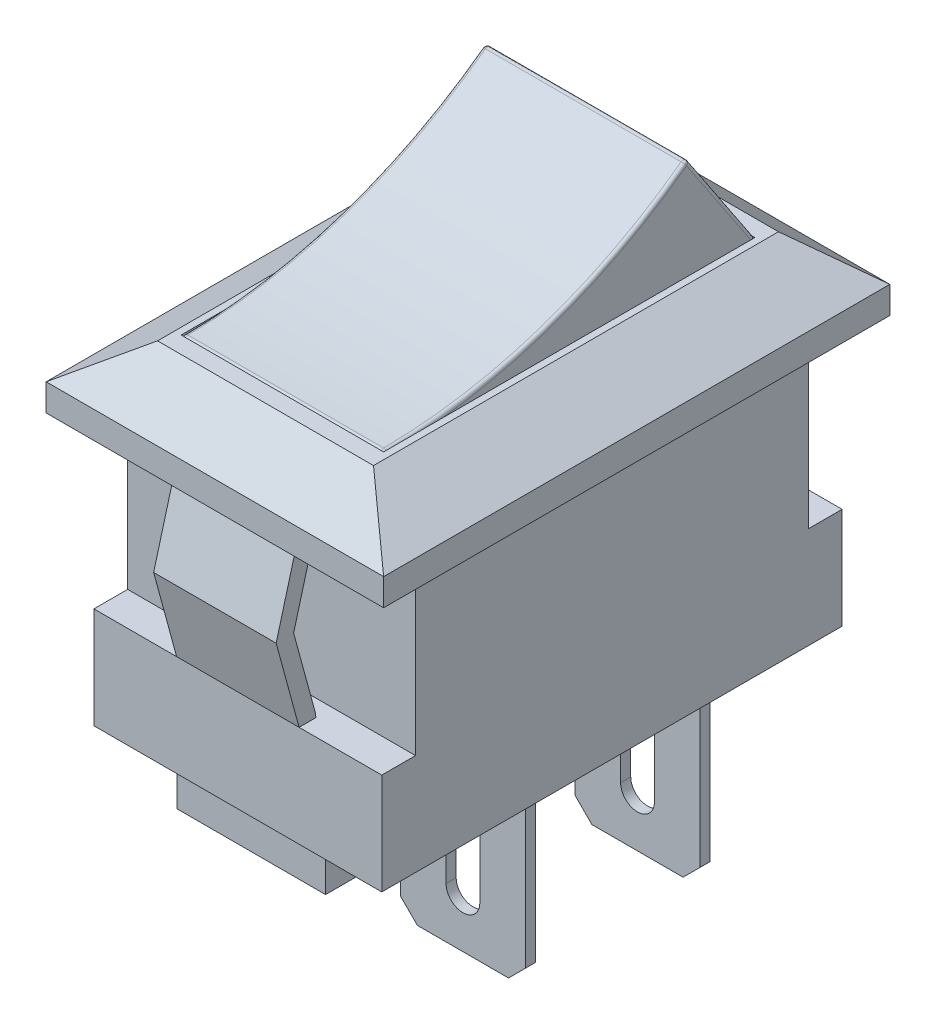
SolidWorks part; units mm, degrees
ref_plane "Front Plane" through (0, 0, 0) normal (0, 0, 1) x (1, 0, 0)
ref_plane "Top Plane" through (0, 0, 0) normal (0, 1, 0) x (1, 0, 0)
ref_plane "Right Plane" through (0, 0, 0) normal (1, 0, 0) x (0, 0, -1)
sketch "Sketch1" plane through (0, 0, 0) normal (0, 1, 0) x (1, 0, 0)
  line L1 (4.265, -6.82) -> (-4.265, -6.82)
  line L2 (4.265, -6.82) -> (4.265, 6.82)
  line L3 (4.265, 6.82) -> (-4.265, 6.82)
  line L4 (-4.265, -6.82) -> (-4.265, 6.82)
  line L5 (4.265, -6.82) -> (-4.265, 6.82) construction
  line L6 (4.265, 6.82) -> (-4.265, -6.82) construction
  point P0 (0, 0)
  dimension "D1" = 13.64
  dimension "D2" = 8.53
extrude "Boss-Extrude1" add sketch "Sketch1" along normal blind 10
sketch "Sketch2" plane through (-4.265, 0, 0) normal (-1, 0, 0) x (0, 0, 1)
  line L0 (-6.82, 10) -> (-6.82, 0) construction
  line L1 (-6.82, 3) -> (-5.82, 3)
  line L2 (-6.82, 3) -> (-6.82, 8)
  line L3 (-6.82, 8) -> (-5.82, 8)
  line L4 (-5.82, 3) -> (-5.82, 8)
  line L5 (6.82, 10) -> (6.82, 0) construction
  line L6 (6.82, 8) -> (5.82, 8)
  line L7 (6.82, 8) -> (6.82, 3)
  line L8 (6.82, 3) -> (5.82, 3)
  line L9 (5.82, 8) -> (5.82, 3)
  line L10 (-6.82, 0) -> (6.82, 0) construction
  line L11 (-6.82, 10) -> (6.82, 10) construction
  dimension "D1" = 1
  dimension "D2" = 1
  dimension "D3" = 3
  dimension "D4" = 3
  dimension "D5" = 2
extrude "Cut-Extrude1" cut sketch "Sketch2" against normal through all
sketch "Sketch3" plane through (0, 10, 0) normal (0, 1, 0) x (1, 0, 0)
  line L1 (3, -5.5) -> (-3, -5.5)
  line L2 (3, -5.5) -> (3, 5.5)
  line L3 (3, 5.5) -> (-3, 5.5)
  line L4 (-3, -5.5) -> (-3, 5.5)
  line L5 (3, -5.5) -> (-3, 5.5) construction
  line L6 (3, 5.5) -> (-3, -5.5) construction
  point P0 (0, 0)
  dimension "D1" = 11
  dimension "D2" = 6
extrude "Cut-Extrude2" cut sketch "Sketch3" against normal blind 0.5
sketch "Sketch4" plane through (0, 10, 0) normal (0, 1, 0) x (1, 0, 0)
  line L1 (5, -7.5) -> (-5, -7.5)
  line L2 (5, -7.5) -> (5, 7.5)
  line L3 (5, 7.5) -> (-5, 7.5)
  line L4 (-5, -7.5) -> (-5, 7.5)
  line L5 (5, -7.5) -> (-5, 7.5) construction
  line L6 (5, 7.5) -> (-5, -7.5) construction
  point P0 (0, 0)
  line M5 (-3, -5.5) -> (-3, 5.5)
  line M6 (-3, 5.5) -> (3, 5.5)
  line M7 (3, 5.5) -> (3, -5.5)
  line M8 (3, -5.5) -> (-3, -5.5)
  line M9 (-4.265, 6.82) -> (-4.265, -6.82)
  line M10 (-4.265, -6.82) -> (4.265, -6.82)
  line M11 (4.265, -6.82) -> (4.265, 6.82)
  line M12 (4.265, 6.82) -> (-4.265, 6.82)
  dimension "D1" = 10
  dimension "D2" = 15
extrude "Boss-Extrude2" add sketch "Sketch4" against normal up to vertex (2 mm away) contours L4 L1 L2 L3 M9 M12 M11 M10 | M12 M9 M10 M11 M8 M5 M6 M7 region at (0, 10, 7.3197) region at (0, 10, -6.6591) up to point (4.265, 8, 6.82)
sketch "Sketch5" plane through (0, 10, 0) normal (0, 1, 0) x (1, 0, 0)
  line L8 (-3.5, 6) -> (-3.5, -6)
  line L9 (-3.5, -6) -> (3.5, -6)
  line L10 (3.5, -6) -> (3.5, 6)
  line L11 (3.5, 6) -> (-3.5, 6)
  line L12 (-3.5, 6) -> (-3.5, -6) construction
  line L13 (-3.5, -6) -> (3.5, -6) construction
  line L14 (3.5, -6) -> (3.5, 6) construction
  line L15 (3.5, 6) -> (-3.5, 6) construction
  dimension "D1" = 0.5
chamfer "Chamfer1" distance 1.5 distance2 1.2 1 edges at (0, 10, 7.5) first distance on face at (0, 10, 0)
chamfer "Chamfer2" distance 1.2 distance2 1.5 1 edges at (0, 10, -7.5) first distance on face at (0, 9, -7.5)
chamfer "Chamfer3" distance 1.8 distance2 1.2 1 edges at (-5, 10, 0) first distance on face at (0, 10, 0)
chamfer "Chamfer4" distance 1.2 distance2 1.8 1 edges at (5, 10, 0) first distance on face at (5, 8.9333, 0)
sketch "Sketch6" plane through (0, 0, 0) normal (1, 0, 0) x (0, 0, -1)
  line L0 (-6.82, 8) -> (-7.5, 5.5)
  line L1 (-7.5, 8) -> (7.5, 8) construction
  line L2 (-7.5, 5.5) -> (-6.82, 3)
  line L3 (-5.82, 8) -> (-5.82, 3) construction
  line L4 (6.32, 3) -> (6.82, 3)
  line L9 (-6.3375, 7.8688) -> (-6.9818, 5.5)
  line L10 (-6.9818, 5.5) -> (-6.3375, 3.1312)
  line L11 (-6.82, 8) -> (-6.3375, 8)
  line L12 (-6.3375, 8) -> (-6.3375, 7.8688)
  line L13 (-6.3375, 3.1312) -> (-6.32, 3)
  line L14 (-5.82, 3) -> (-6.82, 3) construction
  line L15 (-6.32, 3) -> (-6.82, 3)
  line L16 (0, 0) -> (0, 8) construction
  line L17 (-6.82, 0) -> (6.82, 0) construction
  line L18 (6.3375, 3.1312) -> (6.32, 3)
  line L19 (6.3375, 8) -> (6.3375, 7.8688)
  line L20 (6.82, 8) -> (6.3375, 8)
  line L21 (6.9818, 5.5) -> (6.3375, 3.1312)
  line L22 (6.3375, 7.8688) -> (6.9818, 5.5)
  line L23 (7.5, 5.5) -> (6.82, 3)
  line L24 (6.82, 8) -> (7.5, 5.5)
  point P9 (-5.82, 5.5)
  dimension "D1" = 0.5
extrude "Boss-Extrude3" add sketch "Sketch6" along normal mid plane 3.63
sketch "Sketch7" plane through (0, 0, 0) normal (0, -1, 0) x (1, 0, 0)
  line L0 (-4.265, 6.82) -> (4.265, 6.82) construction
  line L1 (3.5, 1.25) -> (-3.5, 1.25)
  line L2 (3.5, 1.25) -> (3.5, -1.25)
  line L3 (3.5, -1.25) -> (-3.5, -1.25)
  line L4 (-3.5, 1.25) -> (-3.5, -1.25)
  line L5 (3.5, 1.25) -> (-3.5, -1.25) construction
  line L6 (3.5, -1.25) -> (-3.5, 1.25) construction
  line L7 (-3.5, -6.42) -> (3.5, -6.42)
  line L8 (-3.5, -6.42) -> (-3.5, -3.92)
  line L9 (-3.5, -3.92) -> (3.5, -3.92)
  line L10 (3.5, -6.42) -> (3.5, -3.92)
  line L11 (-3.5, 3.92) -> (3.5, 3.92)
  line L12 (-3.5, 3.92) -> (-3.5, 6.42)
  line L13 (-3.5, 6.42) -> (3.5, 6.42)
  line L14 (3.5, 3.92) -> (3.5, 6.42)
  point P0 (0, 0)
  dimension "D1" = 2.5
  dimension "D2" = 7
  dimension "D3" = 0.4
  dimension "D4" = 0.4
  dimension "D5" = 2.5
  dimension "D6" = 2.5
extrude "Boss-Extrude4" add sketch "Sketch7" along normal blind 0.3
sketch "Sketch8" plane through (0, -0.3, 0) normal (0, -1, 0) x (1, 0, 0)
  line L0 (3.5, 1.25) -> (-3.5, 1.25) construction
  line L1 (2.2, -1.25) -> (-2.2, -1.25)
  line L2 (2.2, -1.25) -> (2.2, 1.25)
  line L3 (2.2, 1.25) -> (-2.2, 1.25)
  line L4 (-2.2, -1.25) -> (-2.2, 1.25)
  line L5 (2.2, -1.25) -> (-2.2, 1.25) construction
  line L6 (2.2, 1.25) -> (-2.2, -1.25) construction
  line L7 (3.5, 6.42) -> (-3.5, 6.42) construction
  line L8 (2.2, 3.92) -> (-2.2, 3.92)
  line L9 (2.2, 3.92) -> (2.2, 6.42)
  line L10 (2.2, 6.42) -> (-2.2, 6.42)
  line L11 (-2.2, 3.92) -> (-2.2, 6.42)
  line L12 (2.2, 3.92) -> (-2.2, 6.42) construction
  line L13 (2.2, 6.42) -> (-2.2, 3.92) construction
  line L14 (3.5, -3.92) -> (-3.5, -3.92) construction
  line L15 (2.2, -6.42) -> (-2.2, -6.42)
  line L16 (2.2, -6.42) -> (2.2, -3.92)
  line L17 (2.2, -3.92) -> (-2.2, -3.92)
  line L18 (-2.2, -6.42) -> (-2.2, -3.92)
  line L19 (2.2, -6.42) -> (-2.2, -3.92) construction
  line L20 (2.2, -3.92) -> (-2.2, -6.42) construction
  line L21 (-3.5, -6.42) -> (3.5, -6.42) construction
  line L22 (2.5, -0.2) -> (-2.5, -0.2)
  line L23 (2.5, -0.2) -> (2.5, 0.2)
  line L24 (2.5, 0.2) -> (-2.5, 0.2)
  line L25 (-2.5, -0.2) -> (-2.5, 0.2)
  line L26 (2.5, -0.2) -> (-2.5, 0.2) construction
  line L27 (2.5, 0.2) -> (-2.5, -0.2) construction
  line L28 (2.5, -5.37) -> (-2.5, -5.37)
  line L29 (2.5, -5.37) -> (2.5, -4.97)
  line L30 (2.5, -4.97) -> (-2.5, -4.97)
  line L31 (-2.5, -5.37) -> (-2.5, -4.97)
  line L32 (2.5, -5.37) -> (-2.5, -4.97) construction
  line L33 (2.5, -4.97) -> (-2.5, -5.37) construction
  line L34 (2.5, 4.97) -> (-2.5, 4.97)
  line L35 (2.5, 4.97) -> (2.5, 5.37)
  line L36 (2.5, 5.37) -> (-2.5, 5.37)
  line L37 (-2.5, 4.97) -> (-2.5, 5.37)
  line L38 (2.5, 4.97) -> (-2.5, 5.37) construction
  line L39 (2.5, 5.37) -> (-2.5, 4.97) construction
  line L40 (-3.5, 3.92) -> (3.5, 3.92) construction
  line L41 (1.7, 4.42) -> (1.7, 5.92)
  line L46 (1.1867, 4.1897) -> (-1.1867, 6.1503) construction
  line L47 (1.1867, 6.1503) -> (-1.1867, 4.1897) construction
  line L48 (1.7, 5.92) -> (-1.7, 5.92)
  line L49 (-1.7, 4.42) -> (-1.7, 5.92)
  line L50 (1.7, 4.42) -> (-1.7, 4.42)
  line L51 (1.7, -0.75) -> (1.7, 0.75)
  line L52 (1.7, 0.75) -> (-1.7, 0.75)
  line L53 (-1.7, -0.75) -> (-1.7, 0.75)
  line L54 (1.7, -0.75) -> (-1.7, -0.75)
  line L55 (1.7, -5.92) -> (1.7, -4.42)
  line L56 (1.7, -4.42) -> (-1.7, -4.42)
  line L57 (-1.7, -5.92) -> (-1.7, -4.42)
  line L58 (1.7, -5.92) -> (-1.7, -5.92)
  point P0 (0, 0)
  point P8 (0, 5.17)
  point P15 (0, -5.17)
  point P22 (0, 0)
  point P27 (0, -5.17)
  point P32 (0, 5.17)
  point P42 (0, 5.17)
  line M10 (-3.5, -6.42) -> (3.5, -6.42)
  line M12 (3.5, -3.92) -> (-3.5, -3.92)
  dimension "D1" = 0.4
  dimension "D2" = 0.4
  dimension "D3" = 4.4
  dimension "D4" = 4.4
  dimension "D5" = 4.4
  dimension "D6" = 5
  dimension "D7" = 0.5
  dimension "D8" = 0.5
  dimension "D9" = 0.5
extrude "Boss-Extrude5" add sketch "Sketch8" along normal blind 1 contours L36 L49 L48 L41 L9 L10 L11 | L41 L50 L49 L34 L11 L8 L9 | L24 L53 L52 L51 L2 L3 L4 | L51 L54 L53 L22 L4 L1 L2 | L30 L57 L56 L55 L16 L18 M12 | L55 L58 L57 L28 L18 L16 M10 region at (0, -0.3, -0.895) region at (0, -0.3, 0.895) region at (0, -0.3, 4.275) region at (0, -0.3, 6.065) region at (0, -0.3, -6.065) region at (0, -0.3, -4.275)
extrude "Cut-Extrude4" cut sketch "Sketch8<5>" against normal blind 1 contours L31 L30 L29 L28 | L41 L48 L49 L50 | L35 L34 L37 L36 | L51 L52 L53 L54 | L23 L22 L25 L24 | L55 L56 L57 L58
sketch "Sketch8<5>" plane through (0, -0.3, 0) normal (0, -1, 0) x (1, 0, 0) same geometry as "Sketch8"
sketch "Sketch10" plane through (0, 0, 0) normal (0, 0, 1) x (1, 0, 0)
  line L0 (-4.265, 0) -> (4.265, 0) construction
  line L1 (1.85, 0) -> (-1.85, 0)
  line L3 (1.35, -7) -> (-1.35, -7)
  line L4 (-1.85, -1.3) -> (-1.85, -6.5)
  line L5 (1.85, -6.5) -> (1.35, -7)
  line L10 (3.5, 0) -> (-3.5, 0) construction
  line L11 (2.5, -0.3) -> (2.2, -0.3)
  line L12 (2.5, -0.3) -> (2.5, 0)
  line L13 (2.5, 0) -> (-2.5, 0)
  line L14 (-2.5, -0.3) -> (-2.5, 0)
  line L15 (2.2, -1.3) -> (2.2, -0.3) construction
  line L17 (2.2, -0.3) -> (2.2, -1.3)
  line L18 (2.2, -1.3) -> (-2.2, -1.3)
  line L19 (-2.2, -0.3) -> (-2.2, -1.3)
  line L20 (2.2, -1.3) -> (1.85, -1.65)
  line L21 (-2.2, -1.3) -> (-1.85, -1.65)
  line L22 (1.85, -1.3) -> (1.85, -6.5)
  line L23 (-2.2, -0.3) -> (-2.5, -0.3)
  line L24 (0, -5.5) -> (0, -3.7) construction
  line L25 (-0.5, -5.5) -> (-0.5, -3.7)
  line L26 (0.5, -5.5) -> (0.5, -3.7)
  line L27 (-1.35, -7) -> (-1.85, -6.5)
  arc A0 (-0.5, -5.5) -> (0.5, -5.5) centre (0, -5.5) ccw
  arc A1 (0.5, -3.7) -> (-0.5, -3.7) centre (0, -3.7) ccw
  point P1 (-1.85, -7)
  point P2 (1.85, -7)
  point P6 (0, 0)
  point P30 (0, -4.6)
  point P35 (0, -6)
  dimension "D6" = 0.5
  dimension "D1" = 7
  dimension "D2" = 3.7
  dimension "D3" = 45
  dimension "D4" = 45
  dimension "D5" = 1.8
  dimension "D7" = 1
extrude "Boss-Extrude6" add sketch "Sketch10" along normal mid plane 0.3 contours L27 L3 L5 L22 L18 L4 A1 L26 A0 L25 | L23 L19 L18 L17 L11 L12 L13 L1 L14 region at (0, -0.6347, 0) region at (1.782, -1.475, 0)
pattern_linear "LPattern1" count 2 spacing 5.1725 along (0, 0, -1) of "Boss-Extrude6"
sketch "Sketch11" plane through (0, 0, 0) normal (1, 0, 0) x (0, 0, -1)
  line L0 (5.5, 9.5) -> (-5.5, 9.5)
  line L1 (-5.5, 9.5) -> (5.5, 9.5) construction
  line L2 (-5.5, 9.5) -> (-5.5, 9.9003)
  line L3 (-5.5, 10) -> (5.5, 10) construction
  line L4 (5.5, 9.9697) -> (5.5, 9.5)
  line L5 (5.4832, 10.0252) -> (3.5584, 12.9124)
  line L6 (-5.5, 25) -> (-5.5, 10) construction
  line L7 (-5.5, 25) -> (5.1066, 14.3934) construction
  circle A0 centre (-5.5, 25) radius 15 construction
  arc A1 (3.4158, 12.9373) -> (-5.4007, 10.0003) centre (-5.5, 25) cw
  arc A2 (5.4832, 10.0252) -> (5.5, 9.9697) centre (5.4, 9.9697) cw
  arc A3 (3.5584, 12.9124) -> (3.4158, 12.9373) centre (3.4752, 12.8569) ccw
  arc A4 (-5.5, 9.9003) -> (-5.4007, 10.0003) centre (-5.4, 9.9003) cw
  point P19 (3.5, 13)
  dimension "D3" = 45
  dimension "D4" = 0.1
  dimension "D1" = 3
  dimension "D2" = 2
extrude "Boss-Extrude7" add sketch "Sketch11" along normal mid plane 6 separate body
fillet "Fillet1" radius 0.1 14 edges at (-3, 9.7349, -5.5) (-3, 9.9987, -5.4957) (-3, 11.4688, -4.5208) (-3, 12.9554, -3.4925) (-3, 9.7002, 5.5) (-3, 9.9708, 5.4709) (3, 9.7349, -5.5) (3, 9.9987, -5.4957) (3, 11.4688, -4.5208) (3, 12.9554, -3.4925) (3, 9.7002, 5.5) (3, 9.9708, 5.4709) (-3, 10.7689, 0.7593) (3, 10.7689, 0.7593)
